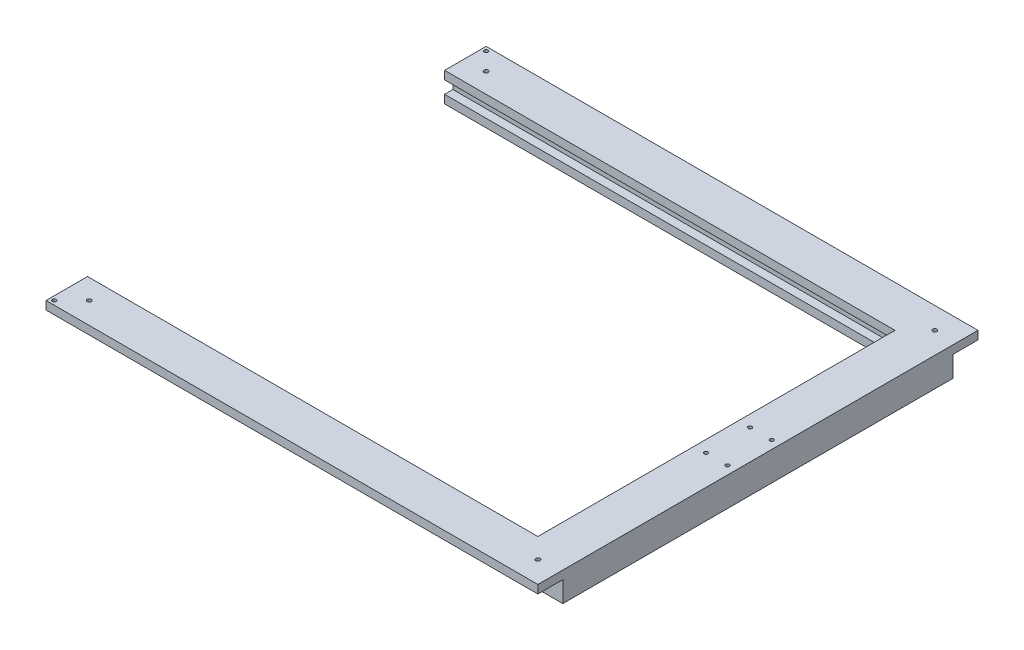
SolidWorks part; units mm, degrees
ref_plane "Спереди" through (0, 0, 0) normal (0, 0, 1) x (1, 0, 0)
ref_plane "Сверху" through (0, 0, 0) normal (0, 1, 0) x (1, 0, 0)
ref_plane "Справа" through (0, 0, 0) normal (1, 0, 0) x (0, 0, -1)
sketch "Эскиз1" plane through (0, 0, 0) normal (0, 1, 0) x (1, 0, 0)
  line L0 (50, -77.9215) -> (50, -607.9215)
  line L1 (-542.3, -77.9215) -> (50, -77.9215)
  line L2 (-542.3, -77.9215) -> (-542.3, -127.9215)
  line L3 (-542.3, -607.9215) -> (50, -607.9215)
  line L5 (-542.3, -127.9215) -> (0, -127.9215)
  line L7 (-542.3, -557.9215) -> (0, -557.9215)
  line L13 (-542.3, -557.9215) -> (-542.3, -607.9215)
  line L22 (0, -127.9215) -> (0, -557.9215)
  dimension "D1" = 592.3
  dimension "D12" = 50
  dimension "D2" = 530
  dimension "D3" = 50
  dimension "D4" = 50
  dimension "D9" = 50
  dimension "D8" = 77.9215
extrude "Бобышка-Вытянуть2" add sketch "Эскиз1" along normal blind 10
sketch "Эскиз2" plane through (0, 0, 0) normal (0, -1, 0) x (1, 0, 0)
  line L0 (-542.3, 127.9215) -> (0, 127.9215) construction
  line L5 (50, 607.9215) -> (50, 77.9215) construction
  line L6 (0, 557.9215) -> (-542.3, 557.9215) construction
  line L18 (50, 577.9215) -> (50, 107.9215)
  line L20 (10, 567.9215) -> (10, 117.9215)
  line L21 (-542.3, 77.9215) -> (-542.3, 127.9215) construction
  line L22 (50, 107.9215) -> (-542.3, 107.9215)
  line L24 (10, 117.9215) -> (-542.3, 117.9215)
  line L25 (-542.3, 107.9215) -> (-542.3, 117.9215)
  line L26 (-542.3, 557.9215) -> (-542.3, 607.9215) construction
  line L27 (50, 577.9215) -> (-542.3, 577.9215)
  line L29 (10, 567.9215) -> (-542.3, 567.9215)
  line L30 (-542.3, 577.9215) -> (-542.3, 567.9215)
  dimension "D1" = 40
  dimension "D2" = 10
  dimension "D3" = 10
  dimension "D4" = 10
  dimension "D5" = 10
extrude "Бобышка-Вытянуть3" add sketch "Эскиз2" along normal blind 15
sketch "Эскиз4" plane through (0, 10, 0) normal (0, 1, 0) x (1, 0, 0)
  line L0 (50, -77.9215) -> (-542.3, -77.9215) construction
  line L1 (-542.3, -77.9215) -> (-542.3, -127.9215) construction
  circle A0 centre (-516.3, -103.9215) radius 2.5
  dimension "D1" = 5
  dimension "D2" = 26
  dimension "D3" = 26
extrude "Вырез-Вытянуть1" cut sketch "Эскиз4" against normal through all
pattern_linear "Линейный массив2" count 2 spacing 540.3 along (1, 0, 0) count 2 spacing 478 along (0, 0, 1) of "Вырез-Вытянуть1"
sketch "Эскиз5" plane through (0, -15, 0) normal (0, -1, 0) x (1, 0, 0)
  line L8 (50, 577.9215) -> (-542.3, 577.9215)
  line L9 (-542.3, 577.9215) -> (-542.3, 557.9215)
  line L10 (-542.3, 557.9215) -> (0, 557.9215)
  line L11 (0, 557.9215) -> (0, 127.9215)
  line L12 (0, 127.9215) -> (-542.3, 127.9215)
  line L13 (-542.3, 127.9215) -> (-542.3, 107.9215)
  line L14 (-542.3, 107.9215) -> (50, 107.9215)
  line L15 (50, 107.9215) -> (50, 577.9215)
extrude "Бобышка-Вытянуть4" add sketch "Эскиз5" along normal blind 10
sketch "Эскиз6" plane through (0, -25, 0) normal (0, -1, 0) x (1, 0, 0)
  line L0 (40, 342.9215) -> (50, 342.9215) construction
  line L1 (40, 316.4215) -> (14, 316.4215) construction
  line L2 (40, 316.4215) -> (40, 369.4215) construction
  line L3 (40, 369.4215) -> (14, 369.4215) construction
  line L4 (14, 316.4215) -> (14, 369.4215) construction
  line L5 (50, 107.9215) -> (50, 577.9215) construction
  circle A1 centre (14, 369.4215) radius 2.25
  circle A2 centre (40, 369.4215) radius 2.25
  circle A3 centre (40, 316.4215) radius 2.25
  circle A4 centre (14, 316.4215) radius 2.25
  point P4 (50, 342.9215)
  point P6 (40, 342.9215)
  dimension "D4" = 4.5
  dimension "D1" = 53
  dimension "D2" = 26
  dimension "D3" = 10
extrude "Вырез-Вытянуть2" cut sketch "Эскиз6" against normal through all
sketch "Эскиз7" plane through (0, 0, 0) normal (0, -1, 0) x (1, 0, 0)
  line L0 (-542.3, 597.9215) -> (-532.3, 607.9215) construction
  line L1 (-542.3, 607.9215) -> (-532.3, 607.9215) construction
  line L2 (-542.3, 607.9215) -> (-542.3, 597.9215) construction
  line L3 (-542.3, 597.9215) -> (-532.3, 597.9215) construction
  line L4 (-532.3, 607.9215) -> (-532.3, 597.9215) construction
  line L5 (-542.3, 607.9215) -> (-532.3, 597.9215) construction
  line L6 (-532.3, 87.9215) -> (-542.3, 77.9215) construction
  line L7 (-542.3, 77.9215) -> (-532.3, 77.9215) construction
  line L8 (-542.3, 77.9215) -> (-542.3, 87.9215) construction
  line L9 (-542.3, 87.9215) -> (-532.3, 87.9215) construction
  line L10 (-532.3, 77.9215) -> (-532.3, 87.9215) construction
  line L11 (-542.3, 87.9215) -> (-532.3, 77.9215) construction
  circle A0 centre (-537.3, 602.9215) radius 2.25
  circle A1 centre (-537.3, 82.9215) radius 2.25
  point P12 (-537.3, 82.9215)
  dimension "D3" = 4.5
  dimension "D6" = 4.5
  dimension "D1" = 10
  dimension "D2" = 10
  dimension "D4" = 10
  dimension "D5" = 10
extrude "Вырез-Вытянуть3" cut sketch "Эскиз7" against normal through all
equation "\"Ширина груза\"= 420"
equation "\"Глубина груза\"= 490"
equation "\"Высота груза\"= 297"
equation "\"Ширина ячейки\"= \"Ширина груза\" + 10"
equation "\"Глубина ячейки\"= \"Глубина груза\" + 10"
equation "\"Высота ячейки\"= \"Высота груза\" + 10 + 13"
equation "\"Колво ячеек ширина\"= 2"
equation "\"Колво ячеек высота\"= 2"
equation "\"Толщина стенки\"= 10"
equation "\"Крепление дверцы\"= 5"
equation "\"Ширина рейки\"= \"Толщина шестерни\""
equation "\"Высота рейки\"= 20"
equation "\"Высота пола\"= 20"
equation "\"Колво полозьев\"= 5"
equation "\"Отступ рейки\"= 20"
equation "\"Глубина каретки\"= \"Глубина ячейки\" + 30 + \"Мотор Y высота корпуса\" + 20"
equation "\"Длинна рейки\"= ( \"Ширина ячейки\" + \"Толщина стенки\" + \"Крепление дверцы\" ) * \"Колво ячеек ширина\" + \"Ширина ячейки выгрузки\" * \"Колво выгрузки\" + \"Толщина стенки\""
equation "\"Отступ шпильки\"= 26"
equation "\"Диаметр шпильки\"= 5"
equation "\"Длинна шпильки\"= ( \"Высота ячейки\" + \"Толщина стенки\" + \"Высота пола\" ) * \"Колво ячеек высота\" + ( \"Толщина стенки\" + \"Отступ рейки\" ) * 2 "
equation "\"D2@Эскиз1\"=\"Ширина ячейки\" + \"Ширина пластины\" * 2 "
equation "\"D9@Эскиз1\"=\"Ширина пластины\""
equation "\"D3@Эскиз1\"=\"Ширина пластины\""
equation "\"D4@Эскиз1\"= \"Ширина пластины\""
equation "\"Ширина пластины\"= 50  "
equation "\"D1@Бобышка-Вытянуть2\"=\"Толщина стенки\""
equation "\"D1@Эскиз4\"= \"Диаметр шпильки\""
equation "\"D4@Линейный массив2\"=\"Ширина ячейки\" + \"Ширина пластины\" * 2  - \"Отступ шпильки\" * 2"
equation "\"D1@Эскиз1\"= \"Глубина каретки\""
equation "\"D3@Линейный массив2\"= \"Глубина каретки\" - \"Отступ шпильки\" * 2"
equation "\"D2@Эскиз4\"=\"Отступ шпильки\""
equation "\"D3@Эскиз4\"= \"Отступ шпильки\""
equation "\"D1@Эскиз2\"= \"Ширина пластины\" - \"Толщина стенки\""
equation "\"D2@Эскиз2\"= \"Толщина стенки\""
equation "\"D3@Эскиз2\"= \"Толщина стенки\""
equation "\"D4@Эскиз2\"= \"Толщина стенки\""
equation "\"D5@Эскиз2\"= \"Толщина стенки\""
equation "\"D1@Бобышка-Вытянуть4\"= \"Толщина стенки\""
equation "\"Вы\"=20"
equation "\"D1@Бобышка-Вытянуть3\"=\"Высота пола\" - 5"
equation "\"Высота зона выгрузки\"= \"Высота ячейки\" * 2 + \"Толщина стенки\" * 2"
equation "\"Колво выгрузки\"= 1"
equation "\"Ширина ячейки выгрузки\"= \"Ширина ячейки\" + \"Толщина стенки\" + \"Отступ крепления мотора фиксации\"*2"
equation "\"Отступ крепления мотора фиксации\" = 30"
equation "\"Мотор X ширина корпуса\"= 42.3"
equation "\"Мотор X высота корпуса\"= 42.3"
equation "\"Мотор X длина корпуса\"= 40"
equation "\"Мотор X вылет вала\"= 19.8"
equation "\"Мотор Y ширина корпуса\"= 42.3"
equation "\"Мотор Y высота корпуса\"= 42.3"
equation "\"Мотор Y длина корпуса\"= 48"
equation "\"Мотор Y вылет вала\"= 30"
equation "\"Мотор Z ширина корпуса\"= 42"
equation "\"Мотор Z высота корпуса\"= 42"
equation "\"Мотор Z длина корпуса\"= 40"
equation "\"Мотор Z вылет вала\"= 23"
equation "\"Мотор диаметр вала ПРЕДВ\"= 5"
equation "\"Мотор шаг крепления ПРЕДВ\"= 31"
equation "\"Мотор диаметр отверстий ПРЕДВ\"= 3"
equation "\"Мотор глубина отверстий ПРЕДВ\"= 4.5"
equation "\"Мотор диаметр буртика ПРЕДВ\"= 22"
equation "\"Мотор высота буртика ПРЕДВ\"= 2"
equation "\"Мотор диаметр шкива ПРЕДВ\"= 16"
equation "\"Мотор длина шкива ПРЕДВ\"= 12"
equation "\"Мотор отступ шкива ПРЕДВ\"= 5"
equation "\"Мотор X шаг градусов\"= 1.8"
equation "\"Мотор X ток А\"= 1.5"
equation "\"Мотор X сопротивление Ом\"= 1.3"
equation "\"Мотор X индуктивность мГн\"= 2"
equation "\"Мотор Y шаг градусов\"= 1.8"
equation "\"Мотор Y ток А\"= 2.2"
equation "\"Мотор Y сопротивление Ом\"= 0.9"
equation "\"Мотор Y индуктивность мГн\"= 2"
equation "\"Мотор Z шаг градусов\"= 1.8"
equation "\"Мотор Z ток А\"= 1"
equation "\"Мотор Z сопротивление Ом\"= 4"
equation "\"Мотор Z индуктивность мГн\"= 8"
equation "\"Мотор Y диаметр ротора\"= 25.78"
